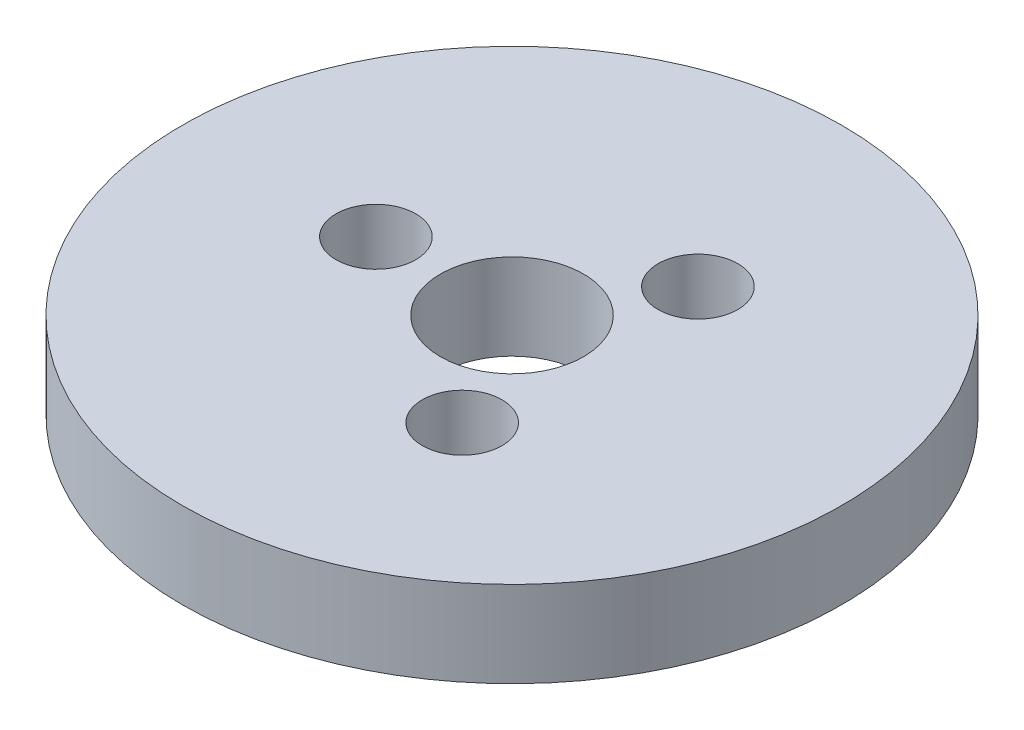
SolidWorks part; units mm, degrees
ref_plane "Front Plane" through (0, 0, 0) normal (0, 0, 1) x (1, 0, 0)
ref_plane "Top Plane" through (0, 0, 0) normal (0, 1, 0) x (1, 0, 0)
ref_plane "Right Plane" through (0, 0, 0) normal (1, 0, 0) x (0, 0, -1)
sketch "Sketch1" plane through (0, 0, 0) normal (0, 1, 0) x (1, 0, 0)
  circle A0 centre (0, 0) radius 57.5
  dimension "FLANGE_OD" = 115
extrude "Boss-Extrude1" add sketch "Sketch1" along normal blind 15
sketch "Sketch2" plane through (0, 0, 0) normal (0, 1, 0) x (1, 0, 0)
  circle A0 centre (0, 0) radius 12.5
  dimension "BORE_D" = 25
extrude "Cut-Extrude1" cut sketch "Sketch2" along normal through all
sketch "Sketch3" plane through (0, 15, 0) normal (0, 1, 0) x (1, 0, 0)
  circle A0 centre (0, 0) radius 23.7476 construction
  circle A1 centre (-23.7476, 0) radius 6.9519
  dimension "BOLT_D" = 13.9038
  dimension "BOLT_PCD" = 47.4951
extrude "Cut-Extrude2" cut sketch "Sketch3" against normal blind 10.8865
pattern_circular "CirPattern1" count 3 over 360 about axis through (0, 0, 0) along (0, 1, 0) of "Cut-Extrude2"
